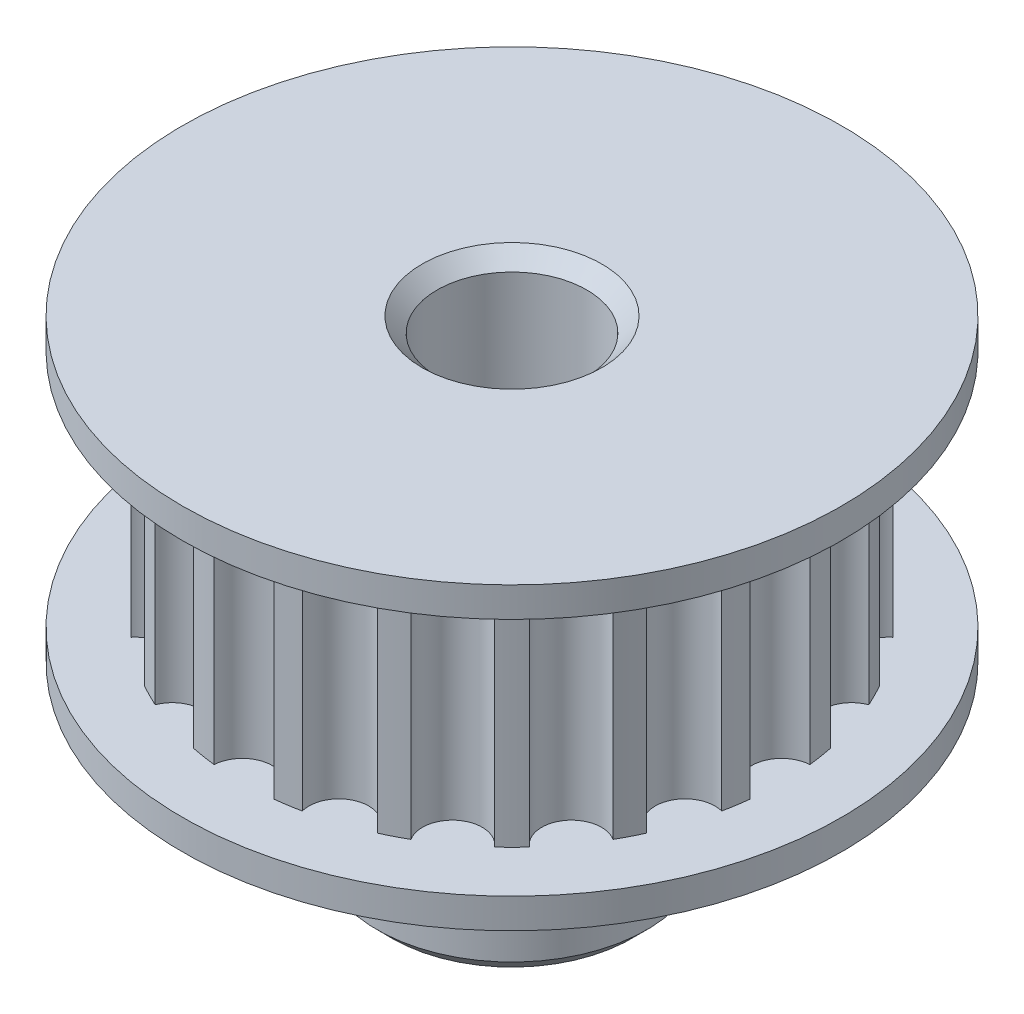
SolidWorks part; units mm, degrees
ref_plane "Alzado" through (0, 0, 0) normal (0, 0, 1) x (1, 0, 0)
ref_plane "Planta" through (0, 0, 0) normal (0, 1, 0) x (1, 0, 0)
ref_plane "Vista lateral" through (0, 0, 0) normal (1, 0, 0) x (0, 0, -1)
sketch "Croquis1" plane through (0, 0, 0) normal (0, 1, 0) x (1, 0, 0)
  circle A0 centre (0, 0) radius 9
  dimension "D1" = 18
extrude "Saliente-Extruir1" add sketch "Croquis1" along normal blind 8
sketch "Croquis3" plane through (0, 8, 0) normal (0, 1, 0) x (1, 0, 0)
  circle A0 centre (0, 0) radius 11
  dimension "D1" = 22
extrude "Saliente-Extruir2" add sketch "Croquis3" along normal blind 1
sketch "Croquis4" plane through (0, 0, 0) normal (0, -1, 0) x (1, 0, 0)
  circle A0 centre (0, 0) radius 11
  circle A1 centre (0, 0) radius 11 construction
extrude "Saliente-Extruir3" add sketch "Croquis4" along normal blind 1
sketch "Croquis5" plane through (0, -1, 0) normal (0, -1, 0) x (1, 0, 0)
  circle A0 centre (0, 0) radius 4.5
  dimension "D1" = 9
extrude "Saliente-Extruir4" add sketch "Croquis5" along normal blind 6
sketch "Croquis6" plane through (0, 9, 0) normal (0, 1, 0) x (1, 0, 0)
  circle A0 centre (0, 0) radius 2.5
  dimension "D1" = 5
extrude "Cortar-Extruir1" cut sketch "Croquis6" against normal through all
sketch "Croquis7" plane through (0, 0, 0) normal (0, 0, 1) x (1, 0, 0)
  line L2 (8.5653, -4) -> (-9.5125, -4) construction
  line L3 (-4.5, -1) -> (4.5, -1) construction
  line L4 (-4.5, -7) -> (4.5, -7) construction
  circle A0 centre (-0.5925, -4) radius 1
  dimension "D1" = 2
extrude "Cortar-Extruir2" cut sketch "Croquis7" against normal through all
sketch "Croquis8" plane through (0, 8, 0) normal (0, -1, 0) x (1, 0, 0)
  line L0 (0, 0) -> (0, -13.2552) construction
  circle A0 centre (0, -9) radius 1
  circle A1 centre (0, 0) radius 9 construction
  dimension "D1" = 2
extrude "Cortar-Extruir5" cut sketch "Croquis8" along normal up to surface (8 mm away) up to face at (0, 0, -11)
pattern_circular "MatrizC1" count 20 over 360 about axis through (0, -7, 0) along (0, 1, 0) of "Cortar-Extruir5"
chamfer "Chaflán1" distance 0.5 angle 45 3 edges at (0, -1, -4.5) (0, -7, -4.5) (0, 9, 2.5)
